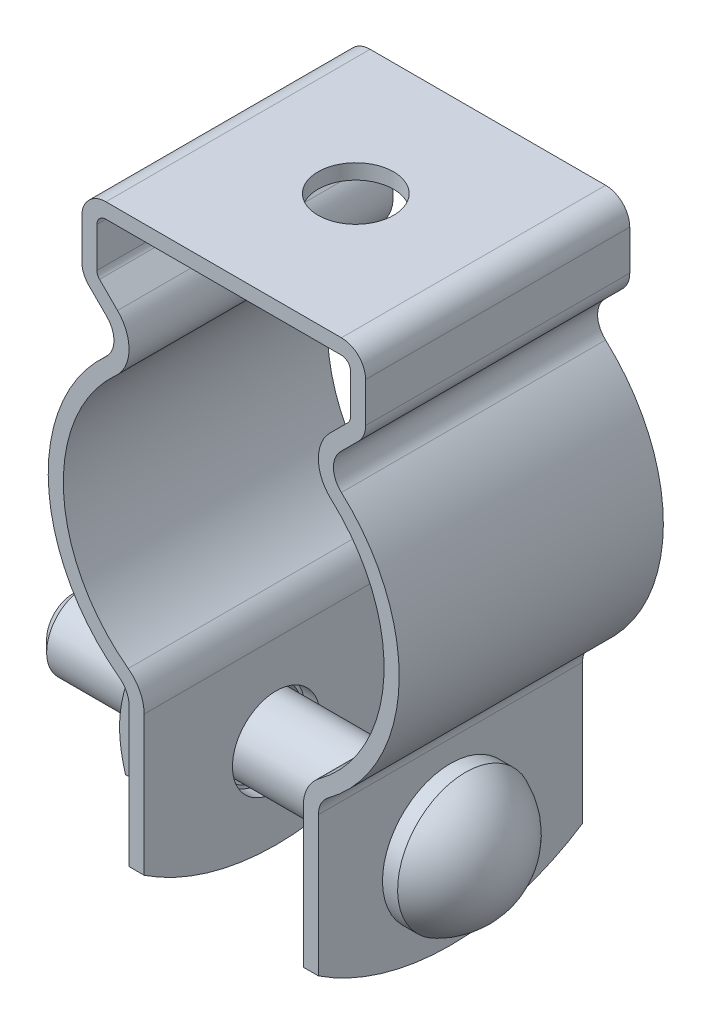
SolidWorks part; units mm, degrees
ref_plane "Front" through (0, 0, 0) normal (0, 0, 1) x (1, 0, 0)
ref_plane "Top" through (0, 0, 0) normal (0, 1, 0) x (1, 0, 0)
ref_plane "Right" through (0, 0, 0) normal (1, 0, 0) x (0, 0, -1)
sketch "Sketch1" plane through (0, 0, 0) normal (0, 0, 1) x (1, 0, 0)
  line L0 (-11.3428, 15.4065) -> (-9.8296, 13.8933)
  line L1 (-11.938, 16.8434) -> (-11.938, 20.193)
  line L2 (-9.906, 22.225) -> (9.906, 22.225)
  line L3 (11.938, 20.193) -> (11.938, 16.8434)
  line L4 (11.3428, 15.4065) -> (9.8296, 13.8933)
  line L5 (-7.9645, -13.497) -> (-7.9645, -28.575)
  line L6 (6.6945, -28.575) -> (6.6945, -13.497)
  line L7 (7.9645, -28.575) -> (7.9645, -13.497)
  line L8 (10.4448, 16.3046) -> (8.9316, 14.7913)
  line L9 (10.668, 20.193) -> (10.668, 16.8434)
  line L10 (-9.906, 20.955) -> (9.906, 20.955)
  line L11 (-10.668, 16.8434) -> (-10.668, 20.193)
  line L12 (-10.4448, 16.3046) -> (-8.9316, 14.7913)
  line L13 (-6.6945, -13.497) -> (-6.6945, -28.575)
  line L14 (-7.9645, -28.575) -> (-6.6945, -28.575)
  line L15 (6.6945, -28.575) -> (7.9645, -28.575)
  line L16 (0, 16.8434) -> (0, 13.4937) construction
  line L17 (-11.938, 16.8434) -> (0, 16.8434) construction
  arc A0 (-9.9034, 10.9495) -> (-8.7871, -11.8641) centre (0, 0) ccw
  arc A1 (-9.8296, 13.8933) -> (-9.9034, 10.9495) centre (-11.2665, 12.4565) cw
  arc A2 (9.8296, 13.8933) -> (9.9034, 10.9495) centre (11.2665, 12.4565) ccw
  arc A3 (8.7871, -11.8641) -> (9.9034, 10.9495) centre (0, 0) ccw
  arc A4 (8.7871, -11.8641) -> (7.9645, -13.497) centre (9.9965, -13.497) ccw
  arc A5 (-7.9645, -13.497) -> (-8.7871, -11.8641) centre (-9.9965, -13.497) ccw
  arc A6 (11.3428, 15.4065) -> (11.938, 16.8434) centre (9.906, 16.8434) ccw
  arc A7 (11.938, 20.193) -> (9.906, 22.225) centre (9.906, 20.193) ccw
  arc A8 (-11.3428, 15.4065) -> (-11.938, 16.8434) centre (-9.906, 16.8434) cw
  arc A9 (-11.938, 20.193) -> (-9.906, 22.225) centre (-9.906, 20.193) cw
  arc A10 (8.0312, -10.8435) -> (6.6945, -13.497) centre (9.9965, -13.497) ccw
  arc A11 (8.0312, -10.8435) -> (9.0515, 10.0076) centre (0, 0) ccw
  arc A12 (8.9316, 14.7913) -> (9.0515, 10.0076) centre (11.2665, 12.4565) ccw
  arc A13 (10.4448, 16.3046) -> (10.668, 16.8434) centre (9.906, 16.8434) ccw
  arc A14 (10.668, 20.193) -> (9.906, 20.955) centre (9.906, 20.193) ccw
  arc A15 (-10.668, 20.193) -> (-9.906, 20.955) centre (-9.906, 20.193) cw
  arc A16 (-10.4448, 16.3046) -> (-10.668, 16.8434) centre (-9.906, 16.8434) cw
  arc A17 (-8.9316, 14.7913) -> (-9.0515, 10.0076) centre (-11.2665, 12.4565) cw
  arc A18 (-9.0515, 10.0076) -> (-8.0312, -10.8435) centre (0, 0) ccw
  arc A19 (-6.6945, -13.497) -> (-8.0312, -10.8435) centre (-9.9965, -13.497) ccw
  point P1 (0, 22.225)
  dimension "D2" = 2.032
  dimension "D1" = 45
extrude "Boss-Extrude1" add sketch "Sketch1" along normal mid plane 22.225
sketch "Sketch2" plane through (0, 0, 0) normal (0, 1, 0) x (1, 0, 0)
  circle A0 centre (0, 0) radius 3.175
  dimension "Mounting Hole Dia" = 6.35
extrude "Cut-Extrude2" cut sketch "Sketch2" along normal through all
sketch "Sketch4" plane through (0, 0, 0) normal (0, 0, 1) x (1, 0, 0)
  line L0 (-23.7855, -17.861) -> (7.9645, -17.861)
  line L1 (7.9645, -17.861) -> (7.9645, -15.321)
  line L2 (7.9645, -15.321) -> (9.2345, -15.321)
  line L3 (13.0445, -15.321) -> (13.0445, -26.751) construction
  line L4 (13.0445, -21.036) -> (-23.7855, -21.036)
  line L5 (-23.7855, -21.036) -> (-23.7855, -17.861)
  line L6 (7.9645, -28.575) -> (7.9645, -13.497) construction
  line L7 (-23.7855, -17.861) -> (-23.7855, -24.211) construction
  line L8 (9.2345, -15.321) -> (10.5045, -15.321) construction
  line L9 (10.5045, -15.321) -> (11.7745, -15.321) construction
  line L10 (11.7745, -15.321) -> (13.0445, -15.321) construction
  arc A0 (9.2345, -15.321) -> (13.0445, -21.036) centre (6.8532, -21.036) cw
  point P6 (7.9645, -21.036)
revolve "Revolve1" add sketch "Sketch4" angle 360 mid plane about L4
sketch "Sketch5" plane through (-23.7855, 0, 0) normal (-1, 0, 0) x (0, 0, 1)
  circle A1 centre (0, -21.036) radius 3.175
  circle A2 centre (0, -21.036) radius 3.175
  dimension "D1" = 0
curve "Helix/Spiral1" [suppressed] pitch 1.27 height 33.02 turns 26
sketch "Sketch8" plane through (0, 0, 0) normal (1, 0, 0) x (0, 0, -1)
  circle A2 centre (0, -21.036) radius 3.683
  circle A3 centre (0, -21.036) radius 3.683
  dimension "D1" = 0.508
extrude "Cut-Extrude5" cut sketch "Sketch8" against normal through all and the other way through all
sketch "Sketch6" plane through (0, 0, 0) normal (0, 0, 1) x (1, 0, 0)
  line L0 (-23.7855, -17.861) -> (-24.8968, -17.861)
  line L1 (-24.8968, -17.861) -> (-24.4205, -18.6859)
  line L2 (-24.4205, -18.6859) -> (-24.2618, -18.6859)
  line L3 (-24.2618, -18.6859) -> (-23.7855, -17.861)
  line L4 (-24.0237, -18.2734) -> (-24.6587, -18.2734) construction
  dimension "D1" = 60
  dimension "D2" = 0.1588
  dimension "D3" = 0.635
sweep "Sweep1" [suppressed] add profiles "Sketch6" path "Helix/Spiral1"
sketch "Sketch7" plane through (7.9645, 0, 0) normal (-1, 0, 0) x (0, 0, 1)
  circle A1 centre (0, -21.036) radius 5.715
  circle A2 centre (0, -21.036) radius 5.715
  dimension "D1" = 0
extrude "Cut-Extrude4" [suppressed] cut sketch "Sketch7" against normal through all
chamfer "Chamfer1" distance 0.9525 angle 45 1 edges at (-23.7855, -17.861, 0)
combine bodies "Combine1" [suppressed] operation type subtract main body 116 bodies to subtract 118
sketch "Sketch9" plane through (-7.9645, 0, 0) normal (-1, 0, 0) x (0, 0, 1)
  line L1 (0, -27.4518) -> (5.5562, -24.2439)
  line L2 (5.5562, -24.2439) -> (5.5562, -17.8281)
  line L3 (5.5562, -17.8281) -> (0, -14.6202)
  line L4 (0, -14.6202) -> (-5.5562, -17.8281)
  line L5 (-5.5562, -17.8281) -> (-5.5562, -24.2439)
  line L6 (-5.5562, -24.2439) -> (0, -27.4518)
  circle A0 centre (0, -21.036) radius 5.5563 construction
  dimension "Hex/Square Nut" = 11.1125
extrude "Boss-Extrude2" add sketch "Sketch9" along normal blind 6.35 separate body
sketch "Sketch10" plane through (-14.3145, 0, 0) normal (-1, 0, 0) x (0, 0, 1)
  circle A0 centre (0, -21.036) radius 5.5563 construction
  circle A1 centre (0, -21.036) radius 5.5563
extrude "Cut-Extrude6" cut sketch "Sketch10" against normal through all draft 60 flip side to cut
sketch "Sketch11" plane through (-7.9645, 0, 0) normal (1, 0, 0) x (0, 0, -1)
  circle A0 centre (0, -21.036) radius 5.5563 construction
  circle A1 centre (0, -21.036) radius 5.5563
extrude "Cut-Extrude7" cut sketch "Sketch11" against normal through all draft 60 flip side to cut
sketch "Sketch12" plane through (-14.3145, 0, 0) normal (-1, 0, 0) x (0, 0, 1)
  circle A0 centre (0, -21.036) radius 3.429
  dimension "D1" = 6.858
extrude "Cut-Extrude8" cut sketch "Sketch12" against normal through all draft 45
sketch "Sketch13" plane through (-7.9645, 0, 0) normal (1, 0, 0) x (0, 0, -1)
  circle A1 centre (0, -21.036) radius 3.429
  circle A2 centre (0, -21.036) radius 3.429
  dimension "D1" = 0
extrude "Cut-Extrude9" cut sketch "Sketch13" against normal through all draft 45
move or copy body "Body-Move/Copy1" [suppressed] bodies to move or copy 119 copy yes number of copies 1 translate (0, 0, 0)
combine bodies "Combine2" [suppressed] operation type subtract main body 125 bodies to subtract 126
sketch "Sketch3" plane through (0, 0, 0) normal (1, 0, 0) x (0, 0, -1)
  line L2 (-11.1125, -28.575) -> (11.1125, -28.575) construction
  line L3 (11.1125, -28.575) -> (11.1125, -13.497) construction
  line L4 (-11.1125, -28.575) -> (-11.1125, -13.497) construction
  line L5 (11.1125, -31.9088) -> (11.1125, -25.2412)
  line L6 (-11.1125, -31.9088) -> (-11.1125, -25.2412)
  line L7 (-11.1125, -31.9088) -> (11.1125, -31.9088)
  arc A0 (-11.1125, -25.2412) -> (11.1125, -25.2412) centre (0, -8.3873) ccw
  dimension "D1" = 3.3337
extrude "Cut-Extrude3" cut sketch "Sketch3" against normal through all and the other way through all
sketch "Sketch14" plane through (0, 0, 0) normal (1, 0, 0) x (0, 0, -1)
  line L0 (-1.016, -12.781) -> (1.016, -29.291) construction
  line L1 (-1.016, -12.781) -> (1.016, -12.781)
  line L2 (-1.016, -12.781) -> (-1.016, -29.291)
  line L3 (-1.016, -29.291) -> (1.016, -29.291)
  line L4 (1.016, -12.781) -> (1.016, -29.291)
  line L5 (-3.175, -20.02) -> (3.175, -20.02)
  line L6 (-3.175, -20.02) -> (-3.175, -22.052)
  line L7 (-3.175, -22.052) -> (3.175, -22.052)
  line L8 (3.175, -20.02) -> (3.175, -22.052)
  line L9 (-3.175, -20.02) -> (3.175, -22.052) construction
  circle A0 centre (0, -21.036) radius 1.016 construction
  dimension "D1" = 2.032
  dimension "D2" = 6.35
  dimension "D3" = 2.54
extrude "Cut-Extrude10" [suppressed] cut sketch "Sketch14" against normal blind 2.54 draft 8 from vertex contours L6 L7 L2 L5 | L2 L5 L4 L1 | L8 L5 L4 L7 | L7 L2 L3 L4 | L2 L7 L4 L5
sketch "Ref1" plane through (0, 0, 0) normal (0, 0, 1) x (1, 0, 0)
  line L0 (7.9645, -17.353) -> (6.6945, -17.353) construction
  line L1 (-6.6945, -17.353) -> (-7.9645, -17.353) construction
  line L2 (6.6945, -24.719) -> (7.9645, -24.719) construction
  line L3 (-7.9645, -24.719) -> (-6.6945, -24.719) construction
  line L4 (7.9645, -17.353) -> (6.6945, -17.353)
  line L5 (-6.6945, -17.353) -> (-7.9645, -17.353)
  line L6 (6.6945, -24.719) -> (7.9645, -24.719)
  line L7 (-7.9645, -24.719) -> (-6.6945, -24.719)
sketch "Sketch15" [suppressed] plane through (-10.6712, 0, 0) normal (1, 0, 0) x (0, 0, -1)
  line L0 (-7.112, -70.3787) -> (-7.112, -62.1664) construction
  line L1 (-7.112, -59.1605) -> (7.112, -59.1605)
  line L2 (-7.112, -59.1605) -> (-7.112, -73.3845)
  line L3 (-7.112, -73.3845) -> (7.112, -73.3845)
  line L4 (7.112, -59.1605) -> (7.112, -73.3845)
  line L5 (7.112, -62.1664) -> (7.112, -70.3787) construction
  line L6 (-7.112, -59.1605) -> (7.112, -73.3845) construction
  circle A0 centre (0, -66.2725) radius 4.2863 construction
  circle A1 centre (0, -66.2725) radius 4.2862
extrude "Boss-Extrude3" [suppressed] add sketch "Sketch15" against normal up to surface (5.4356 mm away)
sketch "Sketch16" [suppressed] plane through (-10.6712, 0, 0) normal (1, 0, 0) x (0, 0, -1)
  line L4 (7.112, -59.1605) -> (-7.112, -59.1605)
  line L5 (7.112, -73.3845) -> (7.112, -59.1605)
  line L6 (-7.112, -73.3845) -> (7.112, -73.3845)
  line L7 (-7.112, -59.1605) -> (-7.112, -73.3845)
  line L8 (7.112, -59.1605) -> (-7.112, -59.1605)
  line L9 (7.112, -73.3845) -> (7.112, -59.1605)
  line L10 (-7.112, -73.3845) -> (7.112, -73.3845)
  line L11 (-7.112, -59.1605) -> (-7.112, -73.3845)
  dimension "D2" = 0
extrude "Cut-Extrude12" [suppressed] cut sketch "Sketch16" against normal through all flip side to cut
sketch "Sketch17" [suppressed] plane through (15.9233, 0, 0) normal (-1, 0, 0) x (0, 0, 1)
  line L1 (0, -97.8565) -> (9.525, -92.3572)
  line L2 (9.525, -92.3572) -> (9.525, -81.3587)
  line L3 (9.525, -81.3587) -> (0, -75.8594)
  line L4 (0, -75.8594) -> (-9.525, -81.3587)
  line L5 (-9.525, -81.3587) -> (-9.525, -92.3572)
  line L6 (-9.525, -92.3572) -> (0, -97.8565)
  circle A0 centre (0, -86.8579) radius 9.525 construction
  circle A1 centre (0, -86.8579) radius 9.525 construction
extrude "Boss-Extrude4" [suppressed] add sketch "Sketch17" against normal up to vertex
sketch "Sketch18" [suppressed] plane through (22.5908, 0, 0) normal (1, 0, 0) x (0, 0, -1)
  circle A0 centre (0, -86.8579) radius 9.525 construction
  circle A1 centre (0, -86.8579) radius 9.525
extrude "Cut-Extrude13" [suppressed] cut sketch "Sketch18" against normal through all draft 60 flip side to cut
sketch "Sketch19" [suppressed] plane through (15.9233, 0, 0) normal (-1, 0, 0) x (0, 0, 1)
  circle A0 centre (0, -86.8579) radius 9.525 construction
  circle A1 centre (0, -86.8579) radius 9.525
extrude "Cut-Extrude14" [suppressed] cut sketch "Sketch19" against normal through all draft 60 flip side to cut
sketch "Sketch20" [suppressed] plane through (15.9233, 0, 0) normal (-1, 0, 0) x (0, 0, 1)
  circle A0 centre (0, -86.8579) radius 6.35
extrude "Boss-Extrude5" [suppressed] add sketch "Sketch20" along normal offset from surface (26.67 mm away) 36.83
delete or keep bodies "Body-Delete1" [suppressed] type delete bodies bodies 128 127
equation "\"D2@Sketch1\" = \"Thickness@Sketch1\" * 1.6"
equation "\"D1@Sketch3\" = \"Wd@Boss-Extrude1\" * .15"
equation "\"D3@Helix/Spiral1\" = \"Screw Lg@Sketch4\" + \"D4@Helix/Spiral1\""
equation "\"D2@Sketch6\" = \"D4@Helix/Spiral1\" * .125"
equation "\"D3@Sketch6\" = \"D4@Helix/Spiral1\" * .5"
equation "\"D1@Chamfer1\" = \"D4@Helix/Spiral1\" * .75"
equation "\"D1@Sketch12\" = \"Screw Dia@Sketch4\" * 1.08"
equation "\"D1@Cut-Extrude10\" = \"Head Ht@Sketch4\" * .5"
